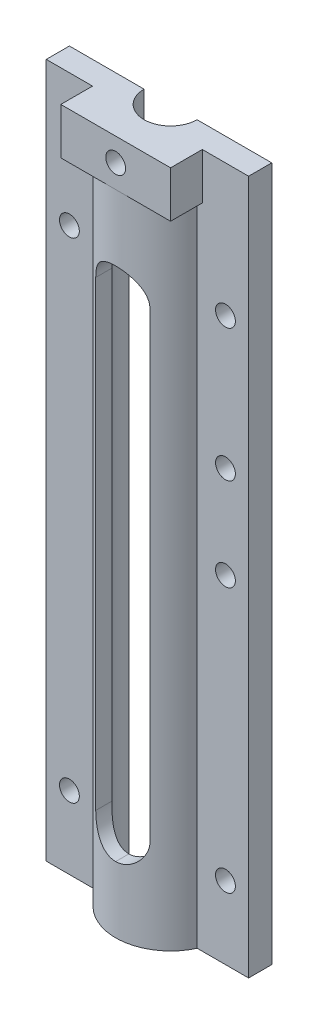
SolidWorks part; units mm, degrees
ref_plane "Front Plane" through (0, 0, 0) normal (0, 0, 1) x (1, 0, 0)
ref_plane "Top Plane" through (0, 0, 0) normal (0, 1, 0) x (1, 0, 0)
ref_plane "Right Plane" through (0, 0, 0) normal (1, 0, 0) x (0, 0, -1)
sketch "Sketch1" plane through (0, 0, 0) normal (0, 1, 0) x (1, 0, 0)
  circle A0 centre (0, 0) radius 6.3
  circle A1 centre (0, 0) radius 8.3
  dimension "D1" = 12.6
  dimension "D2" = 16.6
extrude "Boss-Extrude1" add sketch "Sketch1" along normal blind 95
sketch "Sketch3" plane through (0, 95, 0) normal (0, 1, 0) x (1, 0, 0)
  circle A1 centre (0, 0) radius 8.3
extrude "Boss-Extrude2" add sketch "Sketch3" along normal blind 3
sketch "Sketch4" plane through (0, 95, 0) normal (0, -1, 0) x (-1, 0, 0)
  circle A0 centre (0, 0) radius 1.5
  circle A1 centre (0, 0) radius 6.3
  dimension "D1" = 3
  dimension "D2" = 12.6
sketch "Sketch5" plane through (0, 98, 0) normal (0, 1, 0) x (1, 0, 0)
  line L1 (-8.3, 8.3) -> (8.3, 8.3)
  line L2 (-8.3, 8.3) -> (-8.3, -8.3)
  line L3 (-8.3, -8.3) -> (8.3, -8.3)
  line L4 (8.3, 8.3) -> (8.3, -8.3)
  line L5 (-8.3, 8.3) -> (8.3, -8.3) construction
  line L6 (-8.3, -8.3) -> (8.3, 8.3) construction
  point P0 (0, 0)
extrude "Boss-Extrude4" add sketch "Sketch5" along normal blind 7
sketch "Sketch6" plane through (0, 0, 8.3) normal (0, 0, 1) x (1, 0, 0)
  line L0 (0, 98) -> (0, 88)
  line L2 (0, 10) -> (-4.1, 10)
  line L3 (-4.1, 10) -> (-4.1, 88)
  line L4 (-4.1, 88) -> (4.1, 88)
  line L5 (4.1, 88) -> (4.1, 10)
  line L6 (4.1, 10) -> (0, 10)
  dimension "D1" = 10
  dimension "D2" = 78
  dimension "D3" = 4.1
  dimension "D4" = 8.2
extrude "Cut-Extrude1" cut sketch "Sketch6" against normal through all contours L6 L5 L4 L3 L2 region at (0, 49, 8.3)
fillet "Fillet1" radius 4.1 8 edges at (4.1, 88, -6) (4.1, 88, 6) (-4.1, 88, 6) (-4.1, 88, -6) (4.1, 10, -6) (4.1, 10, 6) (-4.1, 10, -6) (-4.1, 10, 6)
extrude "Cut-Extrude3" cut sketch "Sketch4" against normal blind 3
sketch "Sketch8" plane through (0, 95, 0) normal (0, -1, 0) x (-1, 0, 0)
  circle A0 centre (0, 0) radius 1.5
  dimension "D1" = 3
extrude "Boss-Extrude6" add sketch "Sketch8" along normal blind 2
sketch "Sketch9" plane through (-8.3, 0, 0) normal (-1, 0, 0) x (0, 0, 1)
  line L2 (0, 0) -> (3.5, 0)
  line L3 (3.5, 0) -> (3.5, 105)
  line L4 (3.5, 105) -> (-3.5, 105)
  line L5 (-3.5, 105) -> (-3.5, 0)
  line L6 (-3.5, 0) -> (0, 0)
  dimension "D1" = 3.5
  dimension "D2" = 7
extrude "Boss-Extrude7" add sketch "Sketch9" against normal up to next (2 mm away) and the other way blind 7
mirror "Mirror1" about plane through (0, 0, 0) normal (1, 0, 0) of "Boss-Extrude7"
hole_wizard "Ø3.0 (3) Diameter Hole1" positions "Sketch11" profile "Sketch12" hole size "Ø3.0" standard "ISO" end condition up to next
sketch "Sketch11" plane through (0, 0, 8.3) normal (0, 0, 1) x (1, 0, 0)
  point P0 (0, 101.5)
sketch "Sketch12" plane through (0, 101.5, 8.3) normal (1, 0, 0) x (0, -1, 0)
  line L0 (0, 0) -> (0, 16.6)
  line L1 (0, 16.6) -> (1.5, 16.6)
  line L2 (1.5, 16.6) -> (1.5, 0)
  line L5 (1.5, 0) -> (0, 0)
  line L11 (0, -6.35) -> (0, 107.95) construction
  dimension "Thru Hole Dia." = 3
  dimension "Thru Hole Depth" = 16.6
hole_wizard "Ø3.0 (3) Diameter Hole2" positions "Sketch13" profile "Sketch14" hole size "Ø3.0" standard "ISO" end condition through all
sketch "Sketch13" plane through (0, 0, 3.5) normal (0, 0, 1) x (1, 0, 0)
  line L0 (15.3, 105) -> (8.3, 105) construction
  point P0 (11.8, 85)
  point P4 (11.8, 11)
  point P11 (11.8, 105)
  dimension "D1" = 20
  dimension "D2" = 74
sketch "Sketch14" plane through (11.8, 85, 3.5) normal (1, 0, 0) x (0, -1, 0)
  line L0 (0, 0) -> (0, 11.8)
  line L1 (0, 11.8) -> (1.5, 11.8)
  line L2 (1.5, 11.8) -> (1.5, 0)
  line L5 (1.5, 0) -> (0, 0)
  line L11 (0, -6.35) -> (0, 107.95) construction
  dimension "Thru Hole Dia." = 3
  dimension "Thru Hole Depth" = 11.8
hole_wizard "Ø3.0 (3) Diameter Hole3" positions "Sketch15" profile "Sketch16" hole size "Ø3.0" standard "ISO" end condition through all
sketch "Sketch15" plane through (0, 0, -3.5) normal (0, 0, -1) x (-1, 0, 0)
  line L0 (-15.3, 105) -> (-8.3, 105) construction
  point P0 (-11.8, 65)
  point P5 (-11.8, 105)
  point P6 (-11.8, 51)
  dimension "D1" = 40
  dimension "D2" = 14
sketch "Sketch16" plane through (11.8, 65, -3.5) normal (1, 0, 0) x (0, 1, 0)
  line L0 (0, 0) -> (0, 11.8)
  line L1 (0, 11.8) -> (1.5, 11.8)
  line L2 (1.5, 11.8) -> (1.5, 0)
  line L5 (1.5, 0) -> (0, 0)
  line L11 (0, -6.35) -> (0, 107.95) construction
  dimension "Thru Hole Dia." = 3
  dimension "Thru Hole Depth" = 11.8
mirror "Mirror2" about plane through (0, 0, 0) normal (1, 0, 0) of "Ø3.0 (3) Diameter Hole2"
sketch "Sketch17" plane through (0, 0, 0) normal (0, -1, 0) x (-1, 0, 0)
  line L0 (15.3, 0) -> (4, 0)
  line L1 (15.3, 3.5) -> (15.3, -3.5) construction
  line L2 (-15.3, 0) -> (-4, 0)
  line L3 (-15.3, 3.5) -> (-15.3, -3.5) construction
  line L4 (15.3, 0) -> (15.3, -8.3)
  line L5 (15.3, -8.3) -> (-15.3, -8.3)
  line L6 (-15.3, -8.3) -> (-15.3, 8.3)
  line L7 (-15.3, 8.3) -> (15.3, 8.3)
  line L8 (15.3, 8.3) -> (15.3, 0)
  arc A0 (4, 0) -> (-4, 0) centre (0, 0) cw
  line M8 (15.3, -3.5) -> (15.3, 3.5)
  line M9 (15.3, 3.5) -> (7.526, 3.5)
  arc M10 (7.526, 3.5) -> (-7.526, 3.5) centre (0, 0) ccw
  line M11 (-7.526, 3.5) -> (-15.3, 3.5)
  line M12 (-15.3, 3.5) -> (-15.3, -3.5)
  circle M14 centre (0, 0) radius 6.3
  dimension "D1" = 4
  dimension "D2" = 4
extrude "Cut-Extrude4" cut sketch "Sketch17" against normal through all contours A0 L0 L2 M14 | L2 L0 M12 M14 M8 M9 M10 M11 | L8 L7 M10 M9 | L7 L6 M11 M10 region at (-10.8, 0, -0.3171) region at (0, 0, -1.4179) region at (-10.2031, 0, -6.1309) region at (10.2031, 0, -6.1309)
